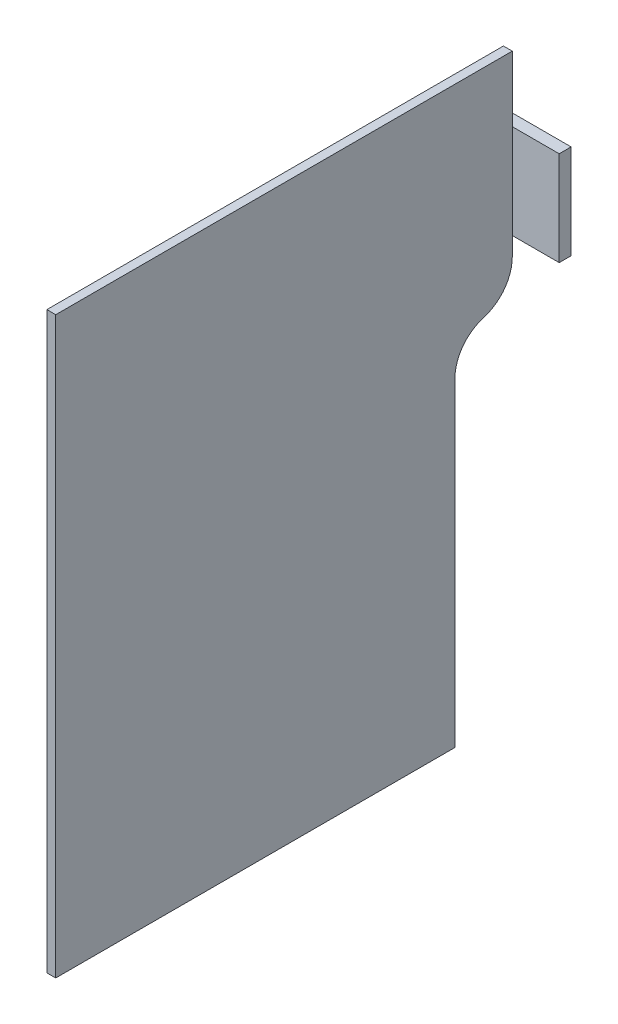
SolidWorks part; units mm, degrees
ref_plane "前视基准面" through (0, 0, 0) normal (0, 0, 1) x (1, 0, 0)
ref_plane "上视基准面" through (0, 0, 0) normal (0, 1, 0) x (1, 0, 0)
ref_plane "右视基准面" through (0, 0, 0) normal (1, 0, 0) x (0, 0, -1)
other "Configuration Table"
sketch "草图1" plane through (0, 0, 0) normal (0, 0, 1) x (1, 0, 0)
  line L1 (-33.7531, 12.2713) -> (-9.996, 12.2713)
  line L2 (-33.7531, 12.2713) -> (-33.7531, -11.4857)
  line L3 (-33.7531, -11.4857) -> (-9.996, -11.4857)
  line L4 (-9.996, 12.2713) -> (-9.996, -11.4857)
extrude "凸台-拉伸1" add sketch "草图1" along normal blind 3
sketch "草图2" plane through (0, 0, 3) normal (0, 0, 1) x (1, 0, 0)
  line L1 (-21.8225, -115.9512) -> (-24.0523, -115.9512)
  line L2 (-21.8225, -115.9512) -> (-21.8225, 28.7501)
  line L3 (-21.8225, 28.7501) -> (-24.0523, 28.7501)
  line L4 (-24.0523, -115.9512) -> (-24.0523, 28.7501)
extrude "凸台-拉伸2" add sketch "草图2" along normal blind 115
fillet "圆角1" radius 20 1 edges at (-24.0523, 0.3928, 3)
sketch "草图3" plane through (-21.8225, 0, 0) normal (1, 0, 0) x (0, 0, -1)
  line L1 (-17.4337, -116.8677) -> (0, -116.8677)
  line L2 (-17.4337, -116.8677) -> (-17.4337, -25.3803)
  line L3 (-17.4337, -25.3803) -> (0, -25.3803)
  line L4 (0, -116.8677) -> (0, -25.3803)
  point P4 (-17.4337, -116.8677)
extrude "切除-拉伸1" cut sketch "草图3" against normal blind 75
fillet "圆角2" radius 10 1 edges at (-22.9374, -25.3803, 17.4337)
fillet "圆角3" radius 10 1 edges at (-22.9374, -25.3803, 3)
